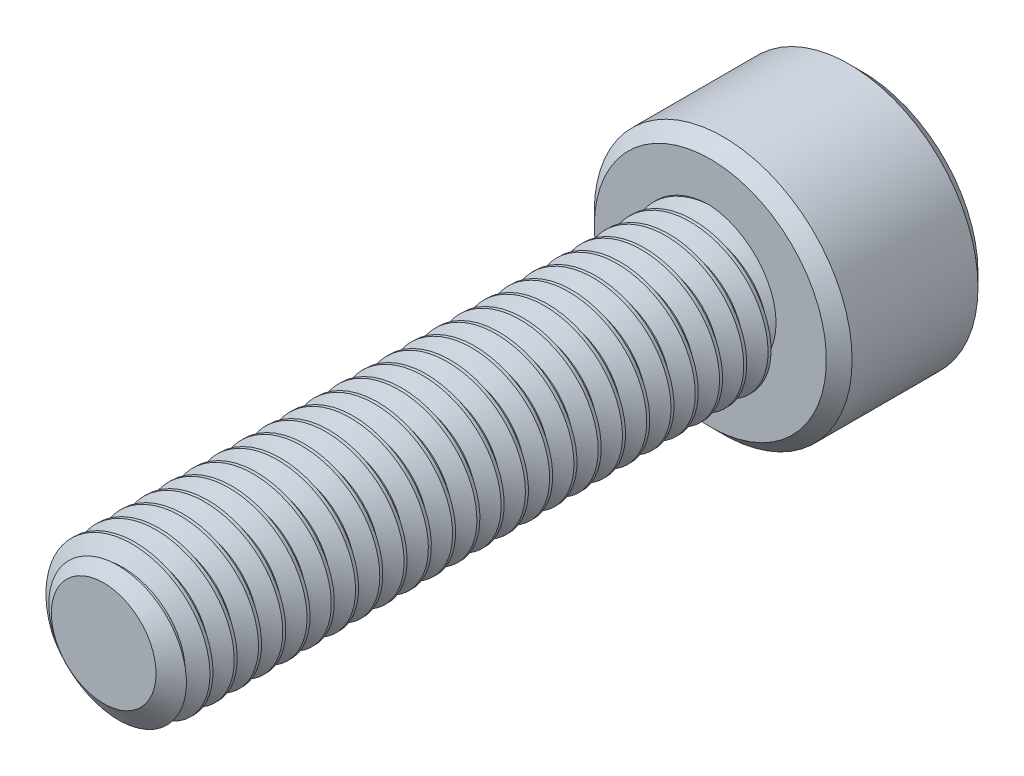
SolidWorks part; units mm, degrees
ref_plane "Front Plane" through (0, 0, 0) normal (0, 0, 1) x (1, 0, 0)
ref_plane "Top Plane" through (0, 0, 0) normal (0, 1, 0) x (1, 0, 0)
ref_plane "Right Plane" through (0, 0, 0) normal (1, 0, 0) x (0, 0, -1)
sketch "Sketch1" plane through (0, 0, 0) normal (0, 0, 1) x (1, 0, 0)
  circle A0 centre (0, 0) radius 2.5
  dimension "OD" = 5
extrude "Extrude1" add sketch "Sketch1" against normal blind 20
sketch "Sketch2" plane through (0, 0, 0) normal (0, 0, 1) x (1, 0, 0)
  circle A0 centre (0, 0) radius 2.5 construction
  circle A1 centre (0, 0) radius 2.5
curve "Helix/Spiral1" pitch 0.8 height 20.8 turns 26 parameters "pitch"=0.8
sketch "Sketch3" plane through (0, 0, 0) normal (1, 0, 0) x (0, 0, -1)
  line L0 (-0.7, 2.5) -> (-0.4, 1.9804)
  line L1 (-0.4, 1.9804) -> (-0.3, 1.9804)
  line L2 (-0.3, 1.9804) -> (0, 2.5)
  line L3 (-0.7, 2.5) -> (0, 2.5)
  line L4 (-0.35, 2.5) -> (-0.35, 1.9804) construction
  line L5 (-0.55, 2.2402) -> (-0.15, 2.2402) construction
  line L6 (0, 2.5) -> (0, -2.5) construction
  dimension "D1" = 0.1
  dimension "D2" = 0.4
  dimension "D3" = 60
sweep "Cut-Sweep1" cut profiles "Sketch3" path "Helix/Spiral1"
sketch "Sketch4" plane through (0, 0, 0) normal (1, 0, 0) x (0, 0, -1)
  line L0 (0.5417, 2.5) -> (0, 1.7264)
  line L1 (0, 1.7264) -> (0, 2.5)
  line L2 (0.5417, 2.5) -> (0, 2.5)
  line L3 (-0.7, 2.5) -> (0, 2.5) construction
  line L4 (0, 0) -> (7.0209, 0) construction
  dimension "D1" = 55
  dimension "D2" = 0.254
revolve "Cut-Revolve1" cut sketch "Sketch4" angle 360 about L4
sketch "Sketch5" plane through (0, 0, 0) normal (1, 0, 0) x (0, 0, -1)
  line L0 (20, -1.991) -> (20, 1.7838) construction
  line L1 (20, 2.627) -> (87.4327, 2.627)
  line L2 (20, 2.627) -> (20, 0)
  line L3 (20, 0) -> (87.3125, 0)
  line L4 (87.3125, 2.2968) -> (87.3125, 0)
  line L5 (87.4327, 2.627) -> (87.3125, 2.2968)
  line L6 (0, 0) -> (9.9695, 0) construction
  point P3 (87.3125, 2.627)
  point P10 (87.3125, 2.627)
  dimension "D1" = 0.3302
  dimension "Thread min" = 87.3125
  dimension "D2" = 0.127
  dimension "D3" = 20
revolve "partially thread" [suppressed] add sketch "Sketch5" angle 360 about L6
sketch "Sketch6" plane through (0, 0, -20) normal (0, 0, -1) x (-1, 0, 0)
  circle A0 centre (0, 0) radius 4.25
  dimension "head dia" = 8.5
extrude "Extrude2" add sketch "Sketch6" along normal blind 5
sketch "Sketch7" plane through (0, 0, -25) normal (0, 0, -1) x (-1, 0, 0)
  line L1 (0, 2.3094) -> (-2, 1.1547)
  line L2 (-2, 1.1547) -> (-2, -1.1547)
  line L3 (-2, -1.1547) -> (0, -2.3094)
  line L4 (0, -2.3094) -> (2, -1.1547)
  line L5 (2, -1.1547) -> (2, 1.1547)
  line L6 (2, 1.1547) -> (0, 2.3094)
  circle A0 centre (0, 0) radius 2 construction
  dimension "hex dia" = 4
extrude "Cut-Extrude1" cut sketch "Sketch7" against normal blind 3
sketch "Sketch8" plane through (0, 0, -25) normal (0, 0, -1) x (-1, 0, 0)
  circle A0 centre (0, 0) radius 2.3094
extrude "Cut-Extrude2" cut sketch "Sketch8" against normal through all draft 45
chamfer "Chamfer1" distance 0.425 angle 45 2 edges at (-4.25, 0, -25) (-4.25, 0, -20)
sketch "Sketch9" plane through (0, 0, 0) normal (1, 0, 0) x (0, 0, -1)
  line L0 (0, 2.5) -> (0, -2.5) construction
  line L1 (4.4, 2.5) -> (4.4, -2.5) construction
  dimension "D1" = 4.4
equation "\"D3@Helix/Spiral1\" = \"screw length@Extrude1\"+\"pitch@Helix/Spiral1\""
equation "\"D1@Sketch3\" = \"pitch@Helix/Spiral1\"*.125"
equation "\"D2@Sketch3\" = \"pitch@Helix/Spiral1\"*.5"
equation "\"D1@Cut-Extrude1\" = \"hex dia@Sketch7\"*.75"
equation "\"D1@Chamfer1\" = \"head dia@Sketch6\"*.05"
equation "\"D1@Sketch9\" = \"pitch@Helix/Spiral1\"*5.5"
